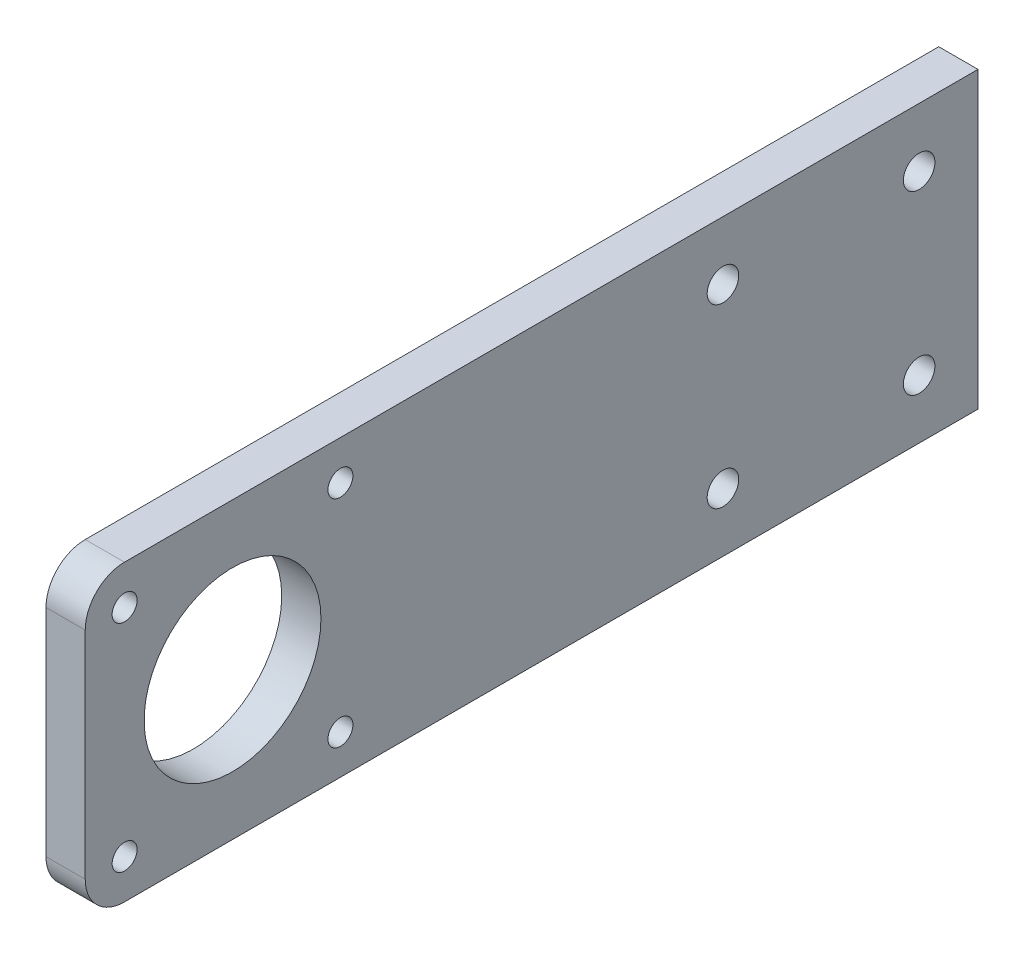
SolidWorks part; units mm, degrees
material "6061-T6 (SS)"
ref_plane "Front" through (0, 0, 0) normal (0, 0, 1) x (1, 0, 0)
ref_plane "Top" through (0, 0, 0) normal (0, 1, 0) x (1, 0, 0)
ref_plane "Right" through (0, 0, 0) normal (1, 0, 0) x (0, 0, -1)
sketch "Sketch1" plane through (0, 0, 0) normal (1, 0, 0) x (0, 0, -1)
  line L0 (0, -23.8125) -> (0, 23.8125)
  line L3 (0, 23.8125) -> (-144.4879, 23.8125)
  line L4 (-144.4879, -23.8125) -> (0, -23.8125)
  line L5 (-144.4879, 23.8125) -> (-144.4879, -23.8125)
  line L6 (-120.65, 23.8125) -> (-120.65, -23.8125) construction
  circle A1 centre (-120.65, 0) radius 14.3129
  point P4 (0, 0)
  dimension "D3" = 28.6258
  dimension "D1" = 9.525
  dimension "D2" = 47.625
  dimension "D5" = 120.65
extrude "Boss-Extrude1" add sketch "Sketch1" along normal blind 6.35
fillet "Fillet1" radius 6.35 2 edges at (3.175, -23.8125, 144.4879) (3.175, 23.8125, 144.4879)
sketch "Sketch4" plane through (0, 0, 0) normal (-1, 0, 0) x (0, 0, 1)
  point P0 (103.1875, 17.4625)
  point P3 (138.1125, 17.4625)
  point P6 (138.1125, -17.4625)
  point P9 (103.1875, -17.4625)
hole_wizard "#10-32 Tapped Hole1" positions "Sketch4" profile "Sketch3" tap size "#10-32" standard "ANSI Inch" end condition up to next
sketch "Sketch3" plane through (0, 17.4625, 103.1875) normal (0, 1, 0) x (0, 0, 1)
  line L0 (0, 0) -> (0, 6.35)
  line L1 (0, 6.35) -> (2.0193, 6.35)
  line L2 (2.0193, 6.35) -> (2.0193, 0)
  line L5 (2.0193, 0) -> (0, 0)
  line L11 (0, -6.35) -> (0, 107.95) construction
  dimension "Thru Tap Drill Dia." = 4.0386
  dimension "Thru Tap Drill Depth" = 6.35
cosmetic thread "Hole Thread1" parameters "D2"=4.826
cosmetic thread "Hole Thread2" parameters "D2"=4.826
cosmetic thread "Hole Thread3" parameters "D2"=4.826
cosmetic thread "Hole Thread4" parameters "D2"=4.826
sketch "Sketch7" plane through (6.35, 0, 0) normal (1, 0, 0) x (0, 0, -1)
  line L0 (-50.8, 23.8125) -> (-50.8, -23.8125) construction
  line L1 (0, 23.8125) -> (-138.1379, 23.8125) construction
  line L2 (-138.1379, -23.8125) -> (0, -23.8125) construction
  line L4 (0, -23.8125) -> (0, 23.8125) construction
  point P0 (-9.525, 14.2875)
  point P2 (-41.275, 14.2875)
  point P4 (-41.275, -14.2875)
  point P6 (-9.525, -14.2875)
  dimension "D1" = 50.8
  dimension "D2" = 9.525
  dimension "D3" = 9.525
  dimension "D4" = 9.525
  dimension "D5" = 9.525
hole_wizard "#10 Clearance Hole1" positions "Sketch7" profile "Sketch6" hole size "#10" standard "ANSI Inch" end condition up to next
sketch "Sketch6" plane through (6.35, 14.2875, 9.525) normal (0, 1, 0) x (0, 0, -1)
  line L0 (0, 0) -> (0, 6.35)
  line L1 (0, 6.35) -> (2.5527, 6.35)
  line L2 (2.5527, 6.35) -> (2.5527, 0)
  line L5 (2.5527, 0) -> (0, 0)
  line L11 (0, -6.35) -> (0, 107.95) construction
  dimension "Thru Hole Dia." = 5.1054
  dimension "Thru Hole Depth" = 6.35
